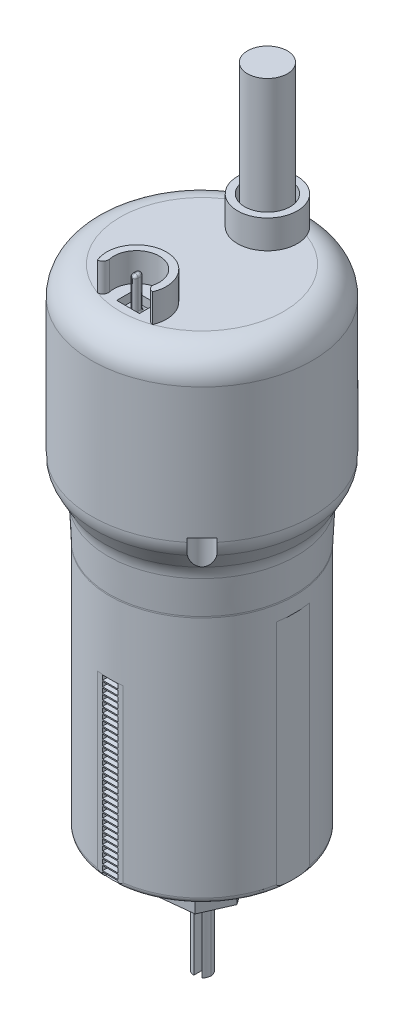
SolidWorks part; units mm, degrees
ref_plane "Plano frontal" through (0, 0, 0) normal (0, 0, 1) x (1, 0, 0)
ref_plane "Plano superior" through (0, 0, 0) normal (0, 1, 0) x (1, 0, 0)
ref_plane "Plano direito" through (0, 0, 0) normal (1, 0, 0) x (0, 0, -1)
sketch "Esboço1" plane through (0, 0, 0) normal (0, 1, 0) x (1, 0, 0)
  circle A0 centre (0, 0) radius 38.75
  dimension "D1" = 77.5
extrude "Ressalto-extrusão1" add sketch "Esboço1" along normal blind 60 and the other way blind 10 draft 29
sketch "Esboço3" plane through (0, -10, 0) normal (0, -1, 0) x (1, 0, 0)
  circle A1 centre (0, 0) radius 33.2069
  circle A2 centre (0, 0) radius 33.2069
  dimension "D1" = 0
extrude "Ressalto-extrusão2" add sketch "Esboço3" along normal blind 14.5 draft 2.75
sketch "Esboço5" plane through (0, -24.5, 0) normal (0, -1, 0) x (1, 0, 0)
  circle A1 centre (0, 0) radius 32.5104
  circle A2 centre (0, 0) radius 32.5104
  dimension "D1" = 0
extrude "Ressalto-extrusão3" add sketch "Esboço5" along normal blind 87.5
sketch "Esboço6" plane through (0, -112, 0) normal (0, -1, 0) x (1, 0, 0)
  circle A0 centre (0, 0) radius 7
  dimension "D1" = 14
extrude "Ressalto-extrusão4" add sketch "Esboço6" along normal blind 6
sketch "Esboço7" plane through (0, -118, 0) normal (0, -1, 0) x (1, 0, 0)
  line L1 (-6.5955, -9.0171) -> (4.5113, -10.2204)
  line L2 (4.5113, -10.2204) -> (11.1067, -1.2033)
  line L3 (11.1067, -1.2033) -> (6.5955, 9.0171)
  line L4 (6.5955, 9.0171) -> (-4.5113, 10.2204)
  line L5 (-4.5113, 10.2204) -> (-11.1067, 1.2033)
  line L6 (-11.1067, 1.2033) -> (-6.5955, -9.0171)
  circle A0 centre (0, 0) radius 9.675 construction
  dimension "D1" = 19.35
extrude "Ressalto-extrusão6" add sketch "Esboço7" along normal blind 12
sketch "Esboço9" plane through (0, -130, 0) normal (0, -1, 0) x (1, 0, 0)
  circle A0 centre (0, 0) radius 3.5
  dimension "D1" = 7
extrude "Corte-extrusão1" cut sketch "Esboço9" against normal blind 30
fillet "Filete1" radius 10 1 edges at (0, 60, 38.75)
sketch "Esboço10" plane through (0, 60, 0) normal (0, 1, 0) x (1, 0, 0)
  line L0 (28.75, 0) -> (-28.75, 0) construction
  line L1 (0, 28.75) -> (0, -28.75) construction
  circle A0 centre (0, 23) radius 10.5
  circle A2 centre (0, 0) radius 28.75 construction
  circle A3 centre (0, 23) radius 8
  arc A4 (-6.1822, -28.0774) -> (6.1822, -28.0774) centre (0, -23) cw
  arc A5 (-9.6783, -27.072) -> (9.6783, -27.072) centre (0, -23) cw
  arc A6 (-9.6783, -27.072) -> (-6.1822, -28.0774) centre (0, 0) ccw
  arc A7 (6.1822, -28.0774) -> (9.6783, -27.072) centre (0, 0) ccw
  dimension "D1" = 21
  dimension "D3" = 16
  dimension "D2" = 23
  dimension "D4" = 23
extrude "Ressalto-extrusão7" add sketch "Esboço10" along normal blind 10
sketch "Esboço11" plane through (0, 60, 0) normal (0, 1, 0) x (1, 0, 0)
  circle A0 centre (0, 23) radius 7
  dimension "D1" = 14
extrude "Ressalto-extrusão8" add sketch "Esboço11" along normal blind 50
fillet "Filete4" radius 2 2 edges at (6.1822, 65, 28.0774) (-6.1822, 65, 28.0774)
sketch "Esboço12" plane through (0, 60, 0) normal (0, 1, 0) x (1, 0, 0)
  line L0 (0, 0) -> (0, -9) construction
  line L1 (-4, -20) -> (4, -20)
  line L2 (-4, -20) -> (-4, -26)
  line L3 (-4, -26) -> (4, -26)
  line L4 (4, -20) -> (4, -26)
  dimension "D1" = 4
  dimension "D2" = 4
  dimension "D3" = 6
  dimension "D4" = 9
  dimension "D5" = 11
extrude "Corte-extrusão2" cut sketch "Esboço12" against normal blind 3
sketch "Esboço13" plane through (0, 57, 0) normal (0, 1, 0) x (1, 0, 0)
  line L0 (-4, -20) -> (-4, -26) construction
  line L1 (-1, -21.5) -> (1, -21.5)
  line L2 (-1, -21.5) -> (-1, -24.5)
  line L3 (-1, -24.5) -> (1, -24.5)
  line L4 (1, -21.5) -> (1, -24.5)
  line L5 (4, -26) -> (4, -20) construction
  line L6 (-4, -26) -> (4, -26) construction
  line L7 (4, -20) -> (-4, -20) construction
  dimension "D1" = 3
  dimension "D2" = 3
  dimension "D3" = 1.5
  dimension "D4" = 1.5
extrude "Ressalto-extrusão9" add sketch "Esboço13" along normal blind 12
fillet "Filete5" radius 1 8 edges at (1, 69, 23) (1, 57, 23) (1, 63, 21.5) (-1, 63, 21.5) (-1, 69, 23) (-1, 57, 23) (-1, 63, 24.5) (1, 63, 24.5)
fillet "Filete6" radius 10 3 edges at (0, 0, 38.75) (0, -10, -33.2069) (0, -24.5, -32.5104)
fillet "Filete7" radius 2 1 edges at (0, -112, -32.5104)
sketch "Esboço16" plane through (0, -112, 0) normal (0, -1, 0) x (1, 0, 0)
  line L0 (0, 30.5104) -> (0, -30.5104) construction
  line L2 (-56.0944, 39.2124) -> (-32, 39.2124)
  line L3 (-56.0944, 39.2124) -> (-56.0944, -45.8266)
  line L4 (-56.0944, -45.8266) -> (-32, -45.8266)
  line L5 (-32, 39.2124) -> (-32, -45.8266)
  line L6 (32, 39.2124) -> (75.2281, 39.2124)
  line L7 (32, 39.2124) -> (32, -45.8266)
  line L8 (32, -45.8266) -> (75.2281, -45.8266)
  line L9 (75.2281, 39.2124) -> (75.2281, -45.8266)
  circle A0 centre (0, 0) radius 30.5104 construction
  dimension "D1" = 32
  dimension "D2" = 32
extrude "Corte-extrusão3" cut sketch "Esboço16" against normal blind 82
sketch "Esboço17" plane through (0, -112, 0) normal (0, -1, 0) x (1, 0, 0)
  line L0 (-30.5104, 0) -> (30.5104, 0) construction
  line L2 (-47.0765, 51.0013) -> (49.0373, 51.0013)
  line L3 (-47.0765, 51.0013) -> (-47.0765, 32.2)
  line L4 (-47.0765, 32.2) -> (49.0373, 32.2)
  line L5 (49.0373, 51.0013) -> (49.0373, 32.2)
  circle A0 centre (0, 0) radius 30.5104 construction
  dimension "D1" = 32.2
extrude "Corte-extrusão6" cut sketch "Esboço17" against normal blind 62
sketch "Esboço18" plane through (0, 0, 32.2) normal (0, 0, 1) x (1, 0, 0)
  line L0 (-4.4819, -50) -> (4.4819, -50) construction
  line L1 (-2.7499, -50.3) -> (2.7501, -50.3)
  line L2 (-2.7499, -50.3) -> (-2.7499, -51.9)
  line L3 (-2.7499, -51.9) -> (2.7501, -51.9)
  line L4 (2.7501, -50.3) -> (2.7501, -51.9)
  line L7 (-2.7499, -53.9) -> (2.7501, -53.9)
  line L8 (-2.7499, -52.3) -> (-2.7499, -53.9)
  line L9 (-2.7499, -52.3) -> (2.7501, -52.3)
  line L10 (2.7501, -52.3) -> (2.7501, -53.9)
  line L11 (-2.7499, -55.9) -> (2.7501, -55.9)
  line L12 (-2.7499, -54.3) -> (-2.7499, -55.9)
  line L13 (-2.7499, -54.3) -> (2.7501, -54.3)
  line L14 (2.7501, -54.3) -> (2.7501, -55.9)
  line L15 (-2.7499, -57.9) -> (2.7501, -57.9)
  line L16 (-2.7499, -56.3) -> (-2.7499, -57.9)
  line L17 (-2.7499, -56.3) -> (2.7501, -56.3)
  line L18 (2.7501, -56.3) -> (2.7501, -57.9)
  line L19 (-2.7499, -59.9) -> (2.7501, -59.9)
  line L20 (-2.7499, -58.3) -> (-2.7499, -59.9)
  line L21 (-2.7499, -58.3) -> (2.7501, -58.3)
  line L22 (2.7501, -58.3) -> (2.7501, -59.9)
  line L23 (-2.7499, -61.9) -> (2.7501, -61.9)
  line L24 (-2.7499, -60.3) -> (-2.7499, -61.9)
  line L25 (-2.7499, -60.3) -> (2.7501, -60.3)
  line L26 (2.7501, -60.3) -> (2.7501, -61.9)
  line L27 (-2.7499, -63.9) -> (2.7501, -63.9)
  line L28 (-2.7499, -62.3) -> (-2.7499, -63.9)
  line L29 (-2.7499, -62.3) -> (2.7501, -62.3)
  line L30 (2.7501, -62.3) -> (2.7501, -63.9)
  line L31 (-2.7499, -65.9) -> (2.7501, -65.9)
  line L32 (-2.7499, -64.3) -> (-2.7499, -65.9)
  line L33 (-2.7499, -64.3) -> (2.7501, -64.3)
  line L34 (2.7501, -64.3) -> (2.7501, -65.9)
  line L35 (-2.7499, -67.9) -> (2.7501, -67.9)
  line L36 (-2.7499, -66.3) -> (-2.7499, -67.9)
  line L37 (-2.7499, -66.3) -> (2.7501, -66.3)
  line L38 (2.7501, -66.3) -> (2.7501, -67.9)
  line L39 (-2.7499, -69.9) -> (2.7501, -69.9)
  line L40 (-2.7499, -68.3) -> (-2.7499, -69.9)
  line L41 (-2.7499, -68.3) -> (2.7501, -68.3)
  line L42 (2.7501, -68.3) -> (2.7501, -69.9)
  line L43 (-2.7499, -71.9) -> (2.7501, -71.9)
  line L44 (-2.7499, -70.3) -> (-2.7499, -71.9)
  line L45 (-2.7499, -70.3) -> (2.7501, -70.3)
  line L46 (2.7501, -70.3) -> (2.7501, -71.9)
  line L47 (-2.7499, -73.9) -> (2.7501, -73.9)
  line L48 (-2.7499, -72.3) -> (-2.7499, -73.9)
  line L49 (-2.7499, -72.3) -> (2.7501, -72.3)
  line L50 (2.7501, -72.3) -> (2.7501, -73.9)
  line L51 (-2.7499, -75.9) -> (2.7501, -75.9)
  line L52 (-2.7499, -74.3) -> (-2.7499, -75.9)
  line L53 (-2.7499, -74.3) -> (2.7501, -74.3)
  line L54 (2.7501, -74.3) -> (2.7501, -75.9)
  line L55 (-2.7499, -77.9) -> (2.7501, -77.9)
  line L56 (-2.7499, -76.3) -> (-2.7499, -77.9)
  line L57 (-2.7499, -76.3) -> (2.7501, -76.3)
  line L58 (2.7501, -76.3) -> (2.7501, -77.9)
  line L59 (-2.7499, -79.9) -> (2.7501, -79.9)
  line L60 (-2.7499, -78.3) -> (-2.7499, -79.9)
  line L61 (-2.7499, -78.3) -> (2.7501, -78.3)
  line L62 (2.7501, -78.3) -> (2.7501, -79.9)
  line L63 (-2.7499, -81.9) -> (2.7501, -81.9)
  line L64 (-2.7499, -80.3) -> (-2.7499, -81.9)
  line L65 (-2.7499, -80.3) -> (2.7501, -80.3)
  line L66 (2.7501, -80.3) -> (2.7501, -81.9)
  line L67 (-2.7499, -83.9) -> (2.7501, -83.9)
  line L68 (-2.7499, -82.3) -> (-2.7499, -83.9)
  line L69 (-2.7499, -82.3) -> (2.7501, -82.3)
  line L70 (2.7501, -82.3) -> (2.7501, -83.9)
  line L71 (-2.7499, -85.9) -> (2.7501, -85.9)
  line L72 (-2.7499, -84.3) -> (-2.7499, -85.9)
  line L73 (-2.7499, -84.3) -> (2.7501, -84.3)
  line L74 (2.7501, -84.3) -> (2.7501, -85.9)
  line L75 (-2.7499, -87.9) -> (2.7501, -87.9)
  line L76 (-2.7499, -86.3) -> (-2.7499, -87.9)
  line L77 (-2.7499, -86.3) -> (2.7501, -86.3)
  line L78 (2.7501, -86.3) -> (2.7501, -87.9)
  line L79 (-2.7499, -89.9) -> (2.7501, -89.9)
  line L80 (-2.7499, -88.3) -> (-2.7499, -89.9)
  line L81 (-2.7499, -88.3) -> (2.7501, -88.3)
  line L82 (2.7501, -88.3) -> (2.7501, -89.9)
  line L83 (-2.7499, -91.9) -> (2.7501, -91.9)
  line L84 (-2.7499, -90.3) -> (-2.7499, -91.9)
  line L85 (-2.7499, -90.3) -> (2.7501, -90.3)
  line L86 (2.7501, -90.3) -> (2.7501, -91.9)
  line L87 (-2.7499, -93.9) -> (2.7501, -93.9)
  line L88 (-2.7499, -92.3) -> (-2.7499, -93.9)
  line L89 (-2.7499, -92.3) -> (2.7501, -92.3)
  line L90 (2.7501, -92.3) -> (2.7501, -93.9)
  line L91 (-2.7499, -95.9) -> (2.7501, -95.9)
  line L92 (-2.7499, -94.3) -> (-2.7499, -95.9)
  line L93 (-2.7499, -94.3) -> (2.7501, -94.3)
  line L94 (2.7501, -94.3) -> (2.7501, -95.9)
  line L95 (-2.7499, -97.9) -> (2.7501, -97.9)
  line L96 (-2.7499, -96.3) -> (-2.7499, -97.9)
  line L97 (-2.7499, -96.3) -> (2.7501, -96.3)
  line L98 (2.7501, -96.3) -> (2.7501, -97.9)
  line L99 (-2.7499, -99.9) -> (2.7501, -99.9)
  line L100 (-2.7499, -98.3) -> (-2.7499, -99.9)
  line L101 (-2.7499, -98.3) -> (2.7501, -98.3)
  line L102 (2.7501, -98.3) -> (2.7501, -99.9)
  line L103 (-2.7499, -101.9) -> (2.7501, -101.9)
  line L104 (-2.7499, -100.3) -> (-2.7499, -101.9)
  line L105 (-2.7499, -100.3) -> (2.7501, -100.3)
  line L106 (2.7501, -100.3) -> (2.7501, -101.9)
  line L107 (-2.7499, -103.9) -> (2.7501, -103.9)
  line L108 (-2.7499, -102.3) -> (-2.7499, -103.9)
  line L109 (-2.7499, -102.3) -> (2.7501, -102.3)
  line L110 (2.7501, -102.3) -> (2.7501, -103.9)
  line L111 (-2.7499, -105.9) -> (2.7501, -105.9)
  line L112 (-2.7499, -104.3) -> (-2.7499, -105.9)
  line L113 (-2.7499, -104.3) -> (2.7501, -104.3)
  line L114 (2.7501, -104.3) -> (2.7501, -105.9)
  line L115 (-2.7499, -107.9) -> (2.7501, -107.9)
  line L116 (-2.7499, -106.3) -> (-2.7499, -107.9)
  line L117 (-2.7499, -106.3) -> (2.7501, -106.3)
  line L118 (2.7501, -106.3) -> (2.7501, -107.9)
  line L119 (-2.7499, -109.9) -> (2.7501, -109.9)
  line L120 (-2.7499, -108.3) -> (-2.7499, -109.9)
  line L121 (-2.7499, -108.3) -> (2.7501, -108.3)
  line L122 (2.7501, -108.3) -> (2.7501, -109.9)
  line L123 (-2.7499, -111.9) -> (2.7501, -111.9)
  line L124 (-2.7499, -110.3) -> (-2.7499, -111.9)
  line L125 (-2.7499, -110.3) -> (2.7501, -110.3)
  line L126 (2.7501, -110.3) -> (2.7501, -111.9)
  line L127 (-4.4819, -110) -> (-4.4819, -50) construction
  dimension "D1" = 0.3
  dimension "D2" = 5.5
  dimension "D3" = 1.732
  dimension "D4" = 1.6
  dimension "D5" = 31
extrude "Corte-extrusão7" cut sketch "Esboço18" against normal blind 2 draft 6
sketch "Esboço19" plane through (0, -30, 0) normal (0, -1, 0) x (1, 0, 0)
  line L0 (-32, 0) -> (32, 0) construction
  line L1 (-27, -27) -> (27, -27) construction
  line L2 (-27, -27) -> (-27, 27) construction
  line L3 (-27, 27) -> (27, 27) construction
  line L4 (27, -27) -> (27, 27) construction
  line L5 (-32, -5.7383) -> (-32, 5.7383) construction
  line L6 (32, 5.7383) -> (32, -5.7383) construction
  line L7 (0, 14.3459) -> (0, -9.5214) construction
  circle A0 centre (-27, 27) radius 3.75
  circle A1 centre (27, 27) radius 3.75
  circle A2 centre (27, -27) radius 3.75
  circle A3 centre (-27, -27) radius 3.75
  dimension "D5" = 7.5
  dimension "D6" = 7.5
  dimension "D7" = 7.5
  dimension "D8" = 7.5
  dimension "D1" = 27
  dimension "D2" = 27
  dimension "D3" = 27
  dimension "D4" = 27
extrude "Corte-extrusão8" cut sketch "Esboço19" against normal blind 34
sketch "Esboço20" plane through (0, -100, 0) normal (0, -1, 0) x (1, 0, 0)
  circle A0 centre (0, 0) radius 3
  dimension "D1" = 6
extrude "Ressalto-extrusão10" add sketch "Esboço20" along normal blind 30
sketch "Esboço21" plane through (0, -130, 0) normal (0, -1, 0) x (1, 0, 0)
  circle A0 centre (0, 0) radius 3.25
  dimension "D1" = 6.5
extrude "Ressalto-extrusão11" add sketch "Esboço21" along normal blind 25
sketch "Esboço23" plane through (0, -155, 0) normal (0, -1, 0) x (1, 0, 0)
  line L0 (0, 2.8696) -> (0, 0)
  line L2 (0, 0) -> (2.2981, 2.2981)
  arc A0 (0, 2.8696) -> (0, -2.8696) centre (0, 0) ccw
  arc A3 (3.25, 0) -> (0, -2.8696) centre (0.1902, 0.1902) cw
  arc A4 (2.2981, 2.2981) -> (3.25, 0) centre (0, 0) ccw
extrude "Corte-extrusão10" cut sketch "Esboço23" against normal blind 25
